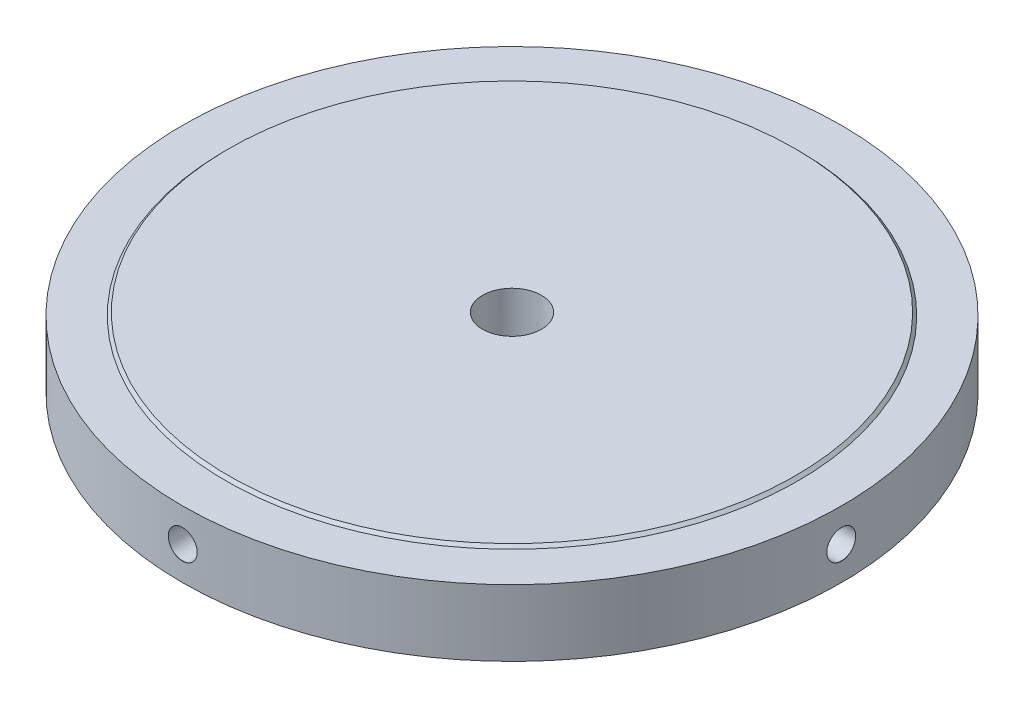
SolidWorks part; units mm, degrees
material "PETG"
ref_plane "Front Plane" through (0, 0, 0) normal (0, 0, 1) x (1, 0, 0)
ref_plane "Top Plane" through (0, 0, 0) normal (0, 1, 0) x (1, 0, 0)
ref_plane "Right Plane" through (0, 0, 0) normal (1, 0, 0) x (0, 0, -1)
sketch "Sketch1" plane through (0, 0, 0) normal (0, 0, 1) x (1, 0, 0)
  line L0 (0, 0) -> (0, 50000) construction
  line L1 (0, 6.25) -> (49, 6.25)
  line L3 (0, 6.25) -> (0, -5.75)
  line L4 (0, -5.75) -> (57, -5.75)
  line L5 (57, 5.75) -> (57, -5.75)
  line L7 (57, 5.75) -> (49.5, 5.75)
  line L10 (49, 6.25) -> (49.5, 5.75)
  point P7 (57, 0)
  dimension "D1" = 11.5
  dimension "D2" = 114
  dimension "D3" = 98
  dimension "D4" = 0.5
  dimension "D5" = 0.5
revolve "Revolve1" add sketch "Sketch1" angle 360 about L0
hole_wizard "Ø5.0mm Dowel Hole1" positions "3DSketch1" profile "Sketch2" hole size "Ø5.0" standard "ISO"
sketch3d "3DSketch1"
  circle A0 centre (0, 0, 0) radius 57 construction
  point P0 (57, 0, 0)
  point P2 (0, 0, 57)
  point P4 (-57, 0, 0)
  point P6 (0, 0, -57)
  point P11 (0, 57, 0)
sketch "Sketch2" plane through (57, 0, 0) normal (0, 1, 0) x (0, 0, -1)
  line L0 (0, 0) -> (0, 13.5022)
  line L1 (0, 13.5022) -> (2.5, 12)
  line L2 (2.5, 12) -> (2.5, 0.025)
  line L3 (2.5, 0.025) -> (2.525, 0)
  line L5 (2.525, 0) -> (0, 0)
  line L6 (-2.5, 0.025) -> (-2.525, 0) construction
  line L10 (0, 13.5022) -> (-2.5, 12) construction
  line L11 (0, -6.35) -> (0, 107.95) construction
  dimension "Hole Dia." = 5
  dimension "Hole Depth" = 12
  dimension "Near C'Sink Dia." = 5.05
  dimension "Near C'Sink Angle" = 90
  dimension "Drill Angle" = 118
hole_wizard "M12 Tapped Hole1" positions "Sketch3" profile "Sketch4" tap size "M12" standard "ISO" end condition up to next
sketch "Sketch3" plane through (0, 6.25, 0) normal (0, 1, 0) x (1, 0, 0)
  point P2 (0, 0)
sketch "Sketch4" plane through (0, 6.25, 0) normal (1, 0, 0) x (0, 0, 1)
  line L0 (0, 0) -> (0, 12)
  line L1 (0, 12) -> (5.1, 12)
  line L2 (5.1, 12) -> (5.1, 0)
  line L5 (5.1, 0) -> (0, 0)
  line L11 (0, -6.35) -> (0, 107.95) construction
  dimension "Thru Tap Drill Dia." = 10.2
  dimension "Thru Tap Drill Depth" = 12
cosmetic thread "Hole Thread10"
equation "\"CanSat_Len\"= 400mm"
equation "\"CanSat_Dia\"= 150mm"
equation "\"BodyTube_ID\"= 114mm"
equation "\"BodyTube_OD\"= 120mm"
equation "\"PayLoadBay_ID\"= 164mm"
equation "\"PayLoadBay_OD\"= 170mm"
equation "\"ParachuteBay_Pitch\"= 300mm"
equation "\"ElectronicsTray_PitchDist\"= 50mm"
equation "\"ElectronicsTray_Height\"= 140mm"
equation "\"D2@Sketch1\"=\"BodyTube_ID\""
